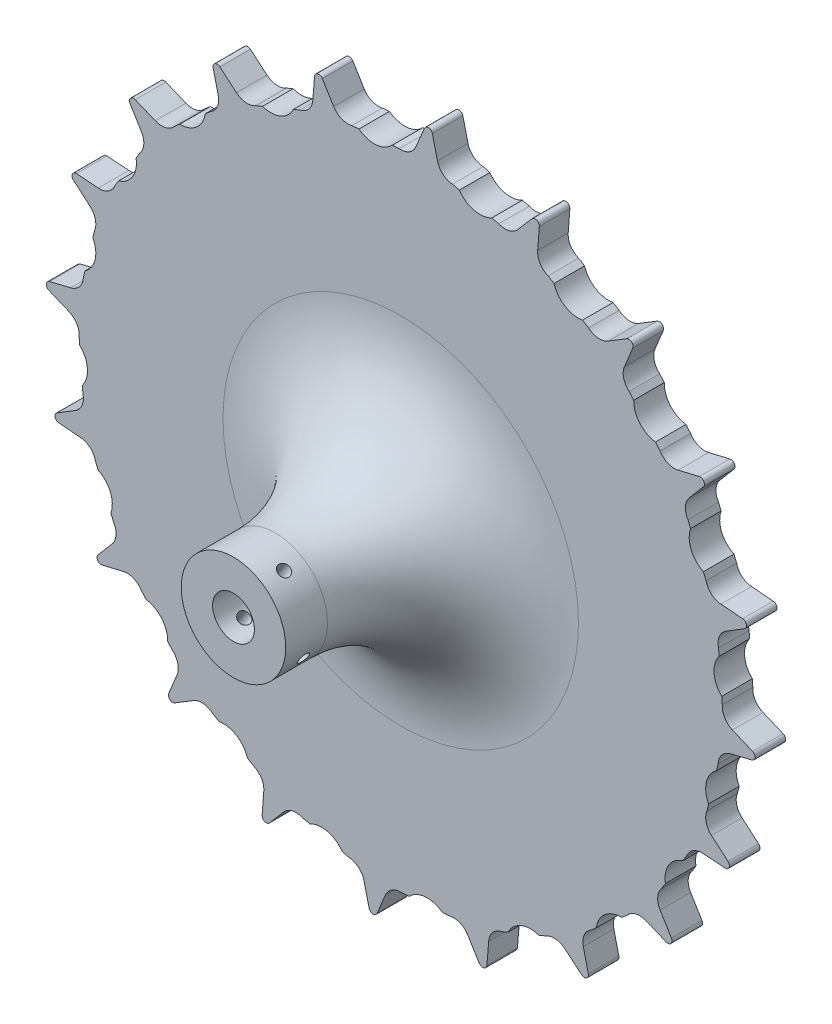
SolidWorks part; units mm, degrees
ref_plane "Front Plane" through (0, 0, 0) normal (0, 0, 1) x (1, 0, 0)
ref_plane "Top Plane" through (0, 0, 0) normal (0, 1, 0) x (1, 0, 0)
ref_plane "Right Plane" through (0, 0, 0) normal (1, 0, 0) x (0, 0, -1)
sketch "Sketch1" plane through (0, 0, 0) normal (0, 0, 1) x (1, 0, 0)
  line L0 (3.6626, 79.3215) -> (5.6677, 84.1262)
  line L1 (3.6626, 79.3215) -> (8.7911, 78.9179) construction
  line L2 (7.5623, 83.9771) -> (8.7911, 78.9179)
  line L3 (3.6626, 79.3215) -> (0, 0) construction
  line L4 (0, 0) -> (8.7911, 78.9179) construction
  line L5 (16.0261, 77.772) -> (18.7582, 82.2038)
  line L6 (20.6061, 81.7602) -> (21.0283, 76.5711)
  line L7 (27.995, 74.3074) -> (31.3867, 78.2573)
  line L8 (33.1425, 77.5301) -> (32.7478, 72.3388)
  line L9 (39.2746, 69.0132) -> (43.2424, 72.3839)
  line L10 (44.8629, 71.3909) -> (43.6609, 66.3253)
  line L11 (49.5871, 62.0196) -> (54.0334, 64.7281)
  line L12 (55.4785, 63.4939) -> (53.4989, 58.6786)
  line L13 (58.6786, 53.4989) -> (63.4939, 55.4785)
  line L14 (64.7281, 54.0334) -> (62.0196, 49.5871)
  line L15 (66.3253, 43.6609) -> (71.3909, 44.8629)
  line L16 (72.3839, 43.2424) -> (69.0132, 39.2746)
  line L17 (72.3388, 32.7478) -> (77.5301, 33.1425)
  line L18 (78.2573, 31.3867) -> (74.3074, 27.995)
  line L19 (76.5711, 21.0283) -> (81.7602, 20.6061)
  line L20 (82.2038, 18.7582) -> (77.772, 16.0261)
  line L21 (78.9179, 8.7911) -> (83.9771, 7.5623)
  line L22 (84.1262, 5.6677) -> (79.3215, 3.6626)
  line L23 (79.3215, -3.6626) -> (84.1262, -5.6677)
  line L24 (83.9771, -7.5623) -> (78.9179, -8.7911)
  line L25 (77.772, -16.0261) -> (82.2038, -18.7582)
  line L26 (81.7602, -20.6061) -> (76.5711, -21.0283)
  line L27 (74.3074, -27.995) -> (78.2573, -31.3867)
  line L28 (77.5301, -33.1425) -> (72.3388, -32.7478)
  line L29 (69.0132, -39.2746) -> (72.3839, -43.2424)
  line L30 (71.3909, -44.8629) -> (66.3253, -43.6609)
  line L31 (62.0196, -49.5871) -> (64.7281, -54.0334)
  line L32 (63.4939, -55.4785) -> (58.6786, -53.4989)
  line L33 (53.4989, -58.6786) -> (55.4785, -63.4939)
  line L34 (54.0334, -64.7281) -> (49.5871, -62.0196)
  line L35 (43.6609, -66.3253) -> (44.8629, -71.3909)
  line L36 (43.2424, -72.3839) -> (39.2746, -69.0132)
  line L37 (32.7478, -72.3388) -> (33.1425, -77.5301)
  line L38 (31.3867, -78.2573) -> (27.995, -74.3074)
  line L39 (21.0283, -76.5711) -> (20.6061, -81.7602)
  line L40 (18.7582, -82.2038) -> (16.0261, -77.772)
  line L41 (8.7911, -78.9179) -> (7.5623, -83.9771)
  line L42 (5.6677, -84.1262) -> (3.6626, -79.3215)
  line L43 (-3.6626, -79.3215) -> (-5.6677, -84.1262)
  line L44 (-7.5623, -83.9771) -> (-8.7911, -78.9179)
  line L45 (-16.0261, -77.772) -> (-18.7582, -82.2038)
  line L46 (-20.6061, -81.7602) -> (-21.0283, -76.5711)
  line L47 (-27.995, -74.3074) -> (-31.3867, -78.2573)
  line L48 (-33.1425, -77.5301) -> (-32.7478, -72.3388)
  line L49 (-39.2746, -69.0132) -> (-43.2424, -72.3839)
  line L50 (-44.8629, -71.3909) -> (-43.6609, -66.3253)
  line L51 (-49.5871, -62.0196) -> (-54.0334, -64.7281)
  line L52 (-55.4785, -63.4939) -> (-53.4989, -58.6786)
  line L53 (-58.6786, -53.4989) -> (-63.4939, -55.4785)
  line L54 (-64.7281, -54.0334) -> (-62.0196, -49.5871)
  line L55 (-66.3253, -43.6609) -> (-71.3909, -44.8629)
  line L56 (-72.3839, -43.2424) -> (-69.0132, -39.2746)
  line L57 (-72.3388, -32.7478) -> (-77.5301, -33.1425)
  line L58 (-78.2573, -31.3867) -> (-74.3074, -27.995)
  line L59 (-76.5711, -21.0283) -> (-81.7602, -20.6061)
  line L60 (-82.2038, -18.7582) -> (-77.772, -16.0261)
  line L61 (-78.9179, -8.7911) -> (-83.9771, -7.5623)
  line L62 (-84.1262, -5.6677) -> (-79.3215, -3.6626)
  line L63 (-79.3215, 3.6626) -> (-84.1262, 5.6677)
  line L64 (-83.9771, 7.5623) -> (-78.9179, 8.7911)
  line L65 (-77.772, 16.0261) -> (-82.2038, 18.7582)
  line L66 (-81.7602, 20.6061) -> (-76.5711, 21.0283)
  line L67 (-74.3074, 27.995) -> (-78.2573, 31.3867)
  line L68 (-77.5301, 33.1425) -> (-72.3388, 32.7478)
  line L69 (-69.0132, 39.2746) -> (-72.3839, 43.2424)
  line L70 (-71.3909, 44.8629) -> (-66.3253, 43.6609)
  line L71 (-62.0196, 49.5871) -> (-64.7281, 54.0334)
  line L72 (-63.4939, 55.4785) -> (-58.6786, 53.4989)
  line L73 (-53.4989, 58.6786) -> (-55.4785, 63.4939)
  line L74 (-54.0334, 64.7281) -> (-49.5871, 62.0196)
  line L75 (-43.6609, 66.3253) -> (-44.8629, 71.3909)
  line L76 (-43.2424, 72.3839) -> (-39.2746, 69.0132)
  line L77 (-32.7478, 72.3388) -> (-33.1425, 77.5301)
  line L78 (-31.3867, 78.2573) -> (-27.995, 74.3074)
  line L79 (-21.0283, 76.5711) -> (-20.6061, 81.7602)
  line L80 (-18.7582, 82.2038) -> (-16.0261, 77.772)
  line L81 (-8.7911, 78.9179) -> (-7.5623, 83.9771)
  line L82 (-5.6677, 84.1262) -> (-3.6626, 79.3215)
  line L83 (0, 80.85) -> (0, 0) construction
  line L84 (0, 0) -> (6.5906, 83.7411) construction
  circle A0 centre (0, 0) radius 80.85 construction
  arc A1 (-3.9676, 80.7526) -> (3.6626, 79.3215) centre (0, 80.85) ccw
  arc A2 (4.2537, 80.738) -> (8.4288, 80.4094) centre (0, 0) cw
  arc A3 (5.6677, 84.1262) -> (7.5623, 83.9771) centre (6.5906, 83.7411) cw
  arc A4 (8.7138, 80.3791) -> (16.0261, 77.772) centre (12.6477, 79.8546) ccw
  arc A5 (18.7582, 82.2038) -> (20.6061, 81.7602) centre (19.6094, 81.6791) cw
  arc A6 (21.1806, 78.0263) -> (27.995, 74.3074) centre (24.984, 76.8929) ccw
  arc A7 (31.3867, 78.2573) -> (33.1425, 77.5301) centre (32.1454, 77.6059) cw
  arc A8 (33.1258, 73.7523) -> (39.2746, 69.0132) centre (36.7051, 72.0379) ccw
  arc A9 (43.2424, 72.3839) -> (44.8629, 71.3909) centre (43.8899, 71.6218) cw
  arc A10 (44.2554, 67.6623) -> (49.5871, 62.0196) centre (47.5224, 65.409) ccw
  arc A11 (54.0334, 64.7281) -> (55.4785, 63.4939) centre (54.5536, 63.8741) cw
  arc A12 (54.2952, 59.9062) -> (58.6786, 53.4989) centre (57.1696, 57.1696) ccw
  arc A13 (63.4939, 55.4785) -> (64.7281, 54.0334) centre (63.8741, 54.5536) cw
  arc A14 (62.9981, 50.675) -> (66.3253, 43.6609) centre (65.409, 47.5224) ccw
  arc A15 (71.3909, 44.8629) -> (72.3839, 43.2424) centre (71.6218, 43.8899) cw
  arc A16 (70.1499, 40.196) -> (72.3388, 32.7478) centre (72.0379, 36.7051) ccw
  arc A17 (77.5301, 33.1425) -> (78.2573, 31.3867) centre (77.6059, 32.1454) cw
  arc A18 (75.5742, 28.7273) -> (76.5711, 21.0283) centre (76.8929, 24.984) ccw
  arc A19 (81.7602, 20.6061) -> (82.2038, 18.7582) centre (81.6791, 19.6094) cw
  arc A20 (79.1377, 16.5512) -> (78.9179, 8.7911) centre (79.8546, 12.6477) ccw
  arc A21 (83.9771, 7.5623) -> (84.1262, 5.6677) centre (83.7411, 6.5906) cw
  arc A22 (80.7526, 3.9676) -> (79.3215, -3.6626) centre (80.85, 0) ccw
  arc A23 (84.1262, -5.6677) -> (83.9771, -7.5623) centre (83.7411, -6.5906) cw
  arc A24 (80.3791, -8.7138) -> (77.772, -16.0261) centre (79.8546, -12.6477) ccw
  arc A25 (82.2038, -18.7582) -> (81.7602, -20.6061) centre (81.6791, -19.6094) cw
  arc A26 (78.0263, -21.1806) -> (74.3074, -27.995) centre (76.8929, -24.984) ccw
  arc A27 (78.2573, -31.3867) -> (77.5301, -33.1425) centre (77.6059, -32.1454) cw
  arc A28 (73.7523, -33.1258) -> (69.0132, -39.2746) centre (72.0379, -36.7051) ccw
  arc A29 (72.3839, -43.2424) -> (71.3909, -44.8629) centre (71.6218, -43.8899) cw
  arc A30 (67.6623, -44.2554) -> (62.0196, -49.5871) centre (65.409, -47.5224) ccw
  arc A31 (64.7281, -54.0334) -> (63.4939, -55.4785) centre (63.8741, -54.5536) cw
  arc A32 (59.9062, -54.2952) -> (53.4989, -58.6786) centre (57.1696, -57.1696) ccw
  arc A33 (55.4785, -63.4939) -> (54.0334, -64.7281) centre (54.5536, -63.8741) cw
  arc A34 (50.675, -62.9981) -> (43.6609, -66.3253) centre (47.5224, -65.409) ccw
  arc A35 (44.8629, -71.3909) -> (43.2424, -72.3839) centre (43.8899, -71.6218) cw
  arc A36 (40.196, -70.1499) -> (32.7478, -72.3388) centre (36.7051, -72.0379) ccw
  arc A37 (33.1425, -77.5301) -> (31.3867, -78.2573) centre (32.1454, -77.6059) cw
  arc A38 (28.7273, -75.5742) -> (21.0283, -76.5711) centre (24.984, -76.8929) ccw
  arc A39 (20.6061, -81.7602) -> (18.7582, -82.2038) centre (19.6094, -81.6791) cw
  arc A40 (16.5512, -79.1377) -> (8.7911, -78.9179) centre (12.6477, -79.8546) ccw
  arc A41 (7.5623, -83.9771) -> (5.6677, -84.1262) centre (6.5906, -83.7411) cw
  arc A42 (3.9676, -80.7526) -> (-3.6626, -79.3215) centre (0, -80.85) ccw
  arc A43 (-5.6677, -84.1262) -> (-7.5623, -83.9771) centre (-6.5906, -83.7411) cw
  arc A44 (-8.7138, -80.3791) -> (-16.0261, -77.772) centre (-12.6477, -79.8546) ccw
  arc A45 (-18.7582, -82.2038) -> (-20.6061, -81.7602) centre (-19.6094, -81.6791) cw
  arc A46 (-21.1806, -78.0263) -> (-27.995, -74.3074) centre (-24.984, -76.8929) ccw
  arc A47 (-31.3867, -78.2573) -> (-33.1425, -77.5301) centre (-32.1454, -77.6059) cw
  arc A48 (-33.1258, -73.7523) -> (-39.2746, -69.0132) centre (-36.7051, -72.0379) ccw
  arc A49 (-43.2424, -72.3839) -> (-44.8629, -71.3909) centre (-43.8899, -71.6218) cw
  arc A50 (-44.2554, -67.6623) -> (-49.5871, -62.0196) centre (-47.5224, -65.409) ccw
  arc A51 (-54.0334, -64.7281) -> (-55.4785, -63.4939) centre (-54.5536, -63.8741) cw
  arc A52 (-54.2952, -59.9062) -> (-58.6786, -53.4989) centre (-57.1696, -57.1696) ccw
  arc A53 (-63.4939, -55.4785) -> (-64.7281, -54.0334) centre (-63.8741, -54.5536) cw
  arc A54 (-62.9981, -50.675) -> (-66.3253, -43.6609) centre (-65.409, -47.5224) ccw
  arc A55 (-71.3909, -44.8629) -> (-72.3839, -43.2424) centre (-71.6218, -43.8899) cw
  arc A56 (-70.1499, -40.196) -> (-72.3388, -32.7478) centre (-72.0379, -36.7051) ccw
  arc A57 (-77.5301, -33.1425) -> (-78.2573, -31.3867) centre (-77.6059, -32.1454) cw
  arc A58 (-75.5742, -28.7273) -> (-76.5711, -21.0283) centre (-76.8929, -24.984) ccw
  arc A59 (-81.7602, -20.6061) -> (-82.2038, -18.7582) centre (-81.6791, -19.6094) cw
  arc A60 (-79.1377, -16.5512) -> (-78.9179, -8.7911) centre (-79.8546, -12.6477) ccw
  arc A61 (-83.9771, -7.5623) -> (-84.1262, -5.6677) centre (-83.7411, -6.5906) cw
  arc A62 (-80.7526, -3.9676) -> (-79.3215, 3.6626) centre (-80.85, 0) ccw
  arc A63 (-84.1262, 5.6677) -> (-83.9771, 7.5623) centre (-83.7411, 6.5906) cw
  arc A64 (-80.3791, 8.7138) -> (-77.772, 16.0261) centre (-79.8546, 12.6477) ccw
  arc A65 (-82.2038, 18.7582) -> (-81.7602, 20.6061) centre (-81.6791, 19.6094) cw
  arc A66 (-78.0263, 21.1806) -> (-74.3074, 27.995) centre (-76.8929, 24.984) ccw
  arc A67 (-78.2573, 31.3867) -> (-77.5301, 33.1425) centre (-77.6059, 32.1454) cw
  arc A68 (-73.7523, 33.1258) -> (-69.0132, 39.2746) centre (-72.0379, 36.7051) ccw
  arc A69 (-72.3839, 43.2424) -> (-71.3909, 44.8629) centre (-71.6218, 43.8899) cw
  arc A70 (-67.6623, 44.2554) -> (-62.0196, 49.5871) centre (-65.409, 47.5224) ccw
  arc A71 (-64.7281, 54.0334) -> (-63.4939, 55.4785) centre (-63.8741, 54.5536) cw
  arc A72 (-59.9062, 54.2952) -> (-53.4989, 58.6786) centre (-57.1696, 57.1696) ccw
  arc A73 (-55.4785, 63.4939) -> (-54.0334, 64.7281) centre (-54.5536, 63.8741) cw
  arc A74 (-50.675, 62.9981) -> (-43.6609, 66.3253) centre (-47.5224, 65.409) ccw
  arc A75 (-44.8629, 71.3909) -> (-43.2424, 72.3839) centre (-43.8899, 71.6218) cw
  arc A76 (-40.196, 70.1499) -> (-32.7478, 72.3388) centre (-36.7051, 72.0379) ccw
  arc A77 (-33.1425, 77.5301) -> (-31.3867, 78.2573) centre (-32.1454, 77.6059) cw
  arc A78 (-28.7273, 75.5742) -> (-21.0283, 76.5711) centre (-24.984, 76.8929) ccw
  arc A79 (-20.6061, 81.7602) -> (-18.7582, 82.2038) centre (-19.6094, 81.6791) cw
  arc A80 (-16.5512, 79.1377) -> (-8.7911, 78.9179) centre (-12.6477, 79.8546) ccw
  arc A81 (-7.5623, 83.9771) -> (-5.6677, 84.1262) centre (-6.5906, 83.7411) cw
  point P289 (0, 0)
  dimension "D1" = 161.7
  dimension "D2" = 3.9688
  dimension "D5" = 1
  dimension "D6" = 84
  dimension "D3" = 4.5
  dimension "D4" = 40
extrude "Boss-Extrude1" add sketch "Sketch1" along normal blind 7.3 contours A81 L81 A80 L80 A79 L79 A78 L78 A77 L77 A76 L76 A75 L75 A74 L74 A73 L73 A72 L72 A71 L71 A70 L70 A69 L69 A68 L68 A67 L67 A66 L66 A65 L65 A64 L64 A63 L63 A62 L62 A61 L61 A60 L60 A59 L59 A58 L58 A57 L57 A56 | A3 L0 A2 L2 region at (-0.0037, -0.0473, 0) region at (6.4765, 82.2915, 0)
sketch "Sketch2" plane through (0, 0, 7.3) normal (0, 0, 1) x (1, 0, 0)
  circle A0 centre (0, 0) radius 12.5
  dimension "D1" = 25
extrude "Boss-Extrude2" add sketch "Sketch2" along normal blind 40
fillet "Fillet1" radius 30 1 edges at (12.5, 0, 7.3)
sketch "Sketch3" plane through (0, 0, 47.3) normal (0, 0, 1) x (1, 0, 0)
  circle A0 centre (0, 0) radius 5
  dimension "D1" = 10
extrude "Cut-Extrude1" cut sketch "Sketch3" against normal through all
hole_wizard "Ø1.0mm Dowel Hole1" positions "3DSketch1" profile "Sketch4" hole size "Ø1.0" standard "ANSI Metric"
sketch3d "3DSketch1"
  point P0 (-6.8176, -10.4771, 42.0201)
  point P2 (-11.0684, 5.8086, 41.6583)
sketch "Sketch4" plane through (-6.8176, -10.4771, 42.0201) normal (0, 0, 1) x (0.8382, -0.5454, 0)
  line L0 (0, 0) -> (0, 34)
  line L1 (0, 34) -> (1.4, 33.1588)
  line L2 (1.4, 33.1588) -> (1.4, 0)
  line L5 (1.4, 0) -> (0, 0)
  line L10 (0, 34) -> (-1.4, 33.1588) construction
  line L11 (0, -6.35) -> (0, 107.95) construction
  dimension "Hole Dia." = 2.8
  dimension "Hole Depth" = 34
  dimension "Drill Angle" = 118
sketch "Sketch5" plane through (0, 0, 0) normal (0, 0, -1) x (-1, 0, 0)
  line L0 (-0.9617, 76.9995) -> (2.0291, 76.7641)
  line L1 (-0.9617, 76.9995) -> (-0.3094, 85.2872)
  line L2 (12.9952, 75.9011) -> (13.6474, 84.1888)
  line L3 (-0.3094, 85.2872) -> (13.6474, 84.1888)
  line L4 (10.0044, 76.1365) -> (12.9952, 75.9011)
  arc A0 (2.0291, 76.7641) -> (10.0044, 76.1365) centre (6.3676, 80.9087) ccw
  arc A2 (7.5623, 83.9771) -> (5.6677, 84.1262) centre (6.5906, 83.7411) ccw construction
  arc A3 (-3.6626, 79.3215) -> (3.6626, 79.3215) centre (0, 80.85) ccw construction
  arc A4 (8.7911, 78.9179) -> (16.0261, 77.772) centre (12.6477, 79.8546) ccw construction
  point P17 (6.669, 84.738)
  dimension "D2" = 3
  dimension "D3" = 3
  dimension "D4" = 6
  dimension "D1" = 14
extrude "Cut-Extrude2" cut sketch "Sketch5" against normal blind 10
pattern_circular "CirPattern1" count 20 over 360 about axis through (0, 0, 0) along (0, 0, 1) of "Cut-Extrude2"
